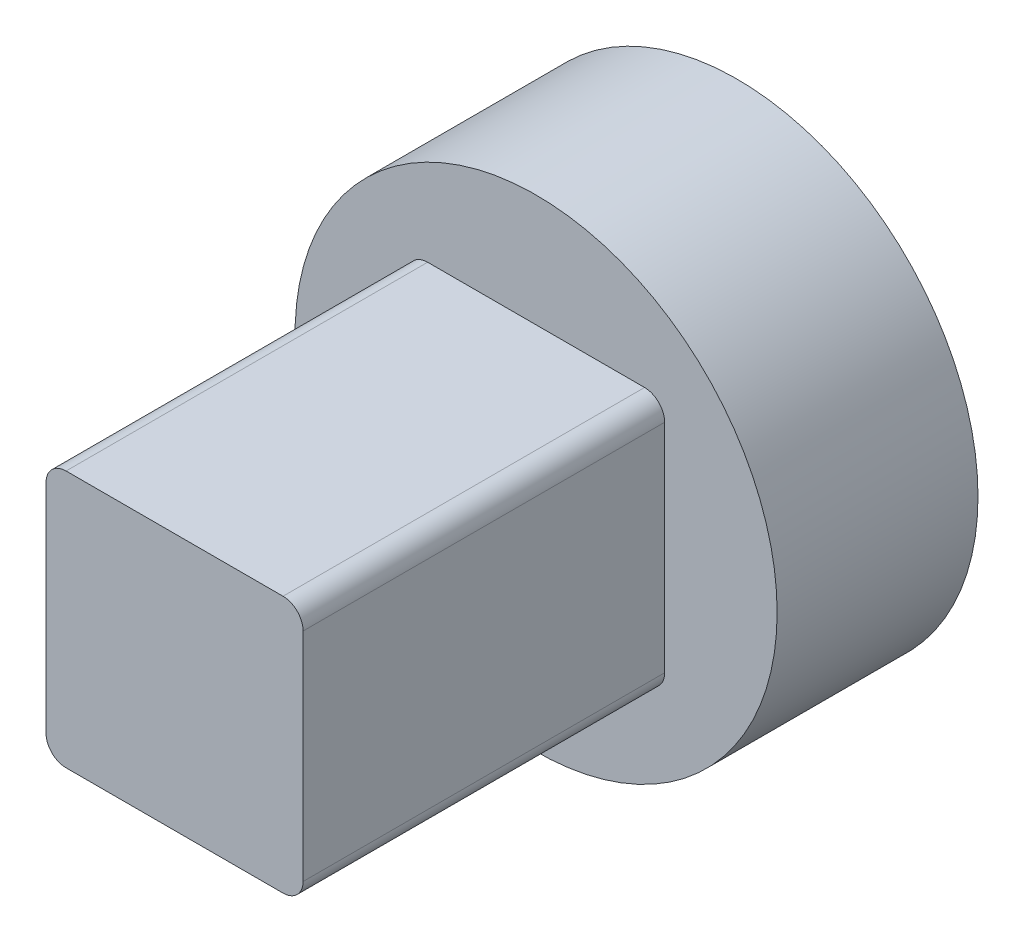
SolidWorks part; units mm, degrees
ref_plane "Front Plane" through (0, 0, 0) normal (0, 0, 1) x (1, 0, 0)
ref_plane "Top Plane" through (0, 0, 0) normal (0, 1, 0) x (1, 0, 0)
ref_plane "Right Plane" through (0, 0, 0) normal (1, 0, 0) x (0, 0, -1)
sketch "Sketch1" plane through (0, 0, -23.4655) normal (0, 0, 1) x (1, 0, 0)
  circle A0 centre (3.7405, -31.8284) radius 2.5
  circle A1 centre (3.7405, -31.8284) radius 6
extrude "Boss-Extrude1" add sketch "Sketch1" along normal blind 5
sketch "Sketch2" plane through (0, 0, -18.4655) normal (0, 0, 1) x (1, 0, 0)
  line L4 (3.7405, -31.8284) -> (6.9405, -31.8284) construction
  line L5 (6.9405, -31.8284) -> (6.9405, -28.6284) construction
  line L7 (6.4405, -28.6284) -> (1.0405, -28.6284)
  line L8 (6.9405, -29.1284) -> (6.9405, -34.5284)
  line L9 (6.4405, -35.0284) -> (1.0405, -35.0284)
  line L10 (0.5405, -29.1284) -> (0.5405, -34.5284)
  arc A1 (0.5405, -29.1284) -> (1.0405, -28.6284) centre (1.0405, -29.1284) cw
  arc A2 (1.0405, -35.0284) -> (0.5405, -34.5284) centre (1.0405, -34.5284) cw
  arc A3 (6.4405, -35.0284) -> (6.9405, -34.5284) centre (6.4405, -34.5284) ccw
  arc A4 (6.4405, -28.6284) -> (6.9405, -29.1284) centre (6.4405, -29.1284) cw
  point P6 (0.5405, -28.6284)
  point P12 (0.5405, -35.0284)
  point P15 (6.9405, -35.0284)
  dimension "D5" = 0.5
  dimension "D6" = 0.5
  dimension "D1" = 3.2
  dimension "D2" = 3.2
  dimension "D3" = 6.4
  dimension "D4" = 6.4
extrude "Boss-Extrude2" add sketch "Sketch2" along normal blind 9
